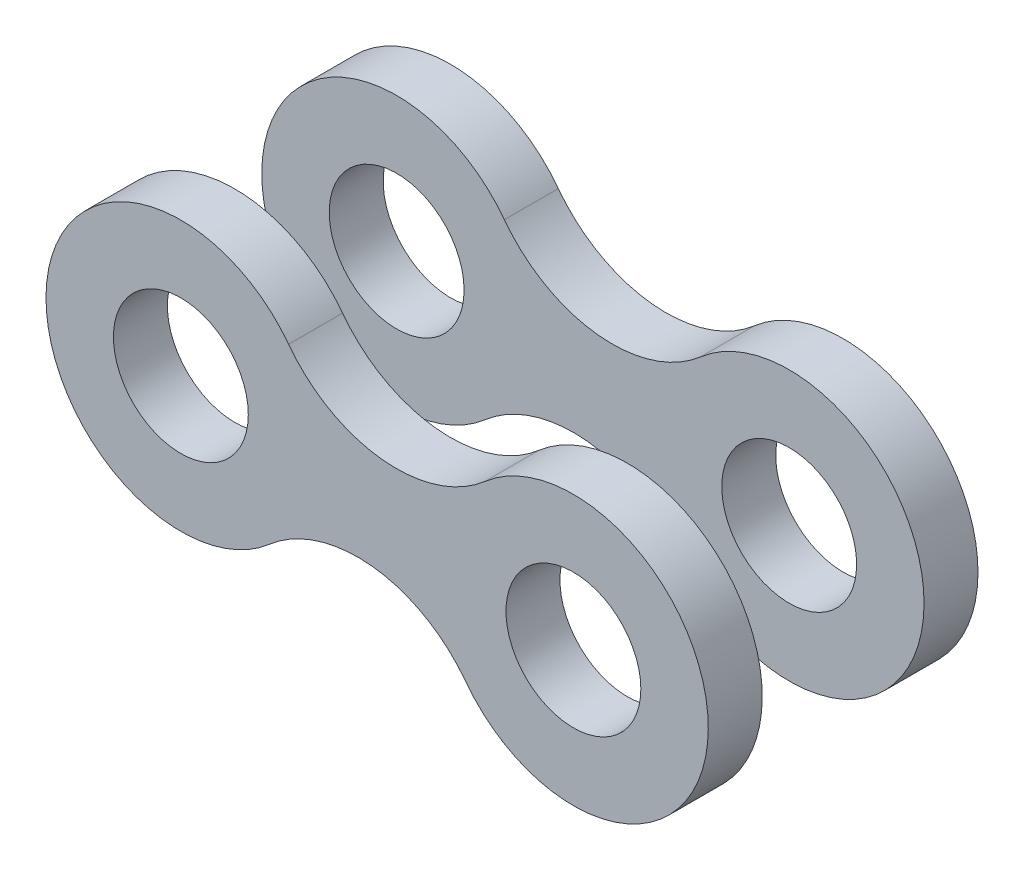
SolidWorks part; units mm, degrees
material "7050-T73510"
ref_plane "Ön Düzlem" through (0, 0, 0) normal (0, 0, 1) x (1, 0, 0)
ref_plane "Üst Düzlem" through (0, 0, 0) normal (0, 1, 0) x (1, 0, 0)
ref_plane "Sağ Düzlem" through (0, 0, 0) normal (1, 0, 0) x (0, 0, -1)
sketch "Çizim2" plane through (0, 0, 0) normal (0, 0, 1) x (1, 0, 0)
  line L0 (0, -73.7578) -> (-232.1205, -73.7578) construction
  line L1 (-24.0045, 69.7424) -> (-243.7247, -5.8828) construction
  line L2 (0, 70) -> (0, 0) construction
  line L3 (-232.1205, -73.7578) -> (0, -73.7578) construction
  line L4 (-243.7247, -5.8828) -> (-24.0045, 69.7424) construction
  line L5 (0, 70) -> (14.5538, 68.4703) construction
  line L6 (0, 70) -> (0, 73.7578) construction
  arc A0 (0, -73.7578) -> (-24.0045, 69.7424) centre (0, 0) ccw construction
  arc A1 (-243.7247, -5.8828) -> (-232.1205, -73.7578) centre (-232.3705, -38.8711) ccw construction
  arc A2 (10.5591, 65.4633) -> (3.2822, 66.2281) centre (6.5644, 62.4562) ccw
  arc A3 (10.5591, 65.4633) -> (11.2716, 72.2422) centre (14.5538, 68.4703) ccw
  arc A4 (11.2716, 72.2422) -> (3.9947, 73.0071) centre (7.9894, 76.0141) cw
  circle A5 centre (0, 70) radius 2.5
  arc A6 (3.9947, 73.0071) -> (3.2822, 66.2281) centre (0, 70) ccw
  circle A7 centre (14.5538, 68.4703) radius 2.5
  dimension "D1" = 10
  dimension "D2" = 5
  dimension "D3" = 70
  dimension "D4" = 3.7578
extrude "Yükseklik-Ekstrüzyon1" add sketch "Çizim2" against normal blind 2
extrude "Yükseklik-Ekstrüzyon2" add sketch "Çizim2<2>" against normal blind 2 from offset 8 separate body offset against normal yes
sketch "Çizim2<2>" plane through (0, 0, 0) normal (0, 0, 1) x (1, 0, 0) same geometry as "Çizim2"
sketch "Çizim3" plane through (0, 0, 0) normal (0, 0, 1) x (1, 0, 0)
  line L0 (0, 70) -> (14.5538, 68.4703) construction
sketch "Çizim4" plane through (0, 0, 0) normal (0, 1, 0) x (1, 0, 0)
  line L3 (-5, 5) -> (19.5538, 5) construction
ref_plane "ortaakisdüzlem" through (0, 0, -5) normal (0, 0, 1) x (1, 0, 0)
